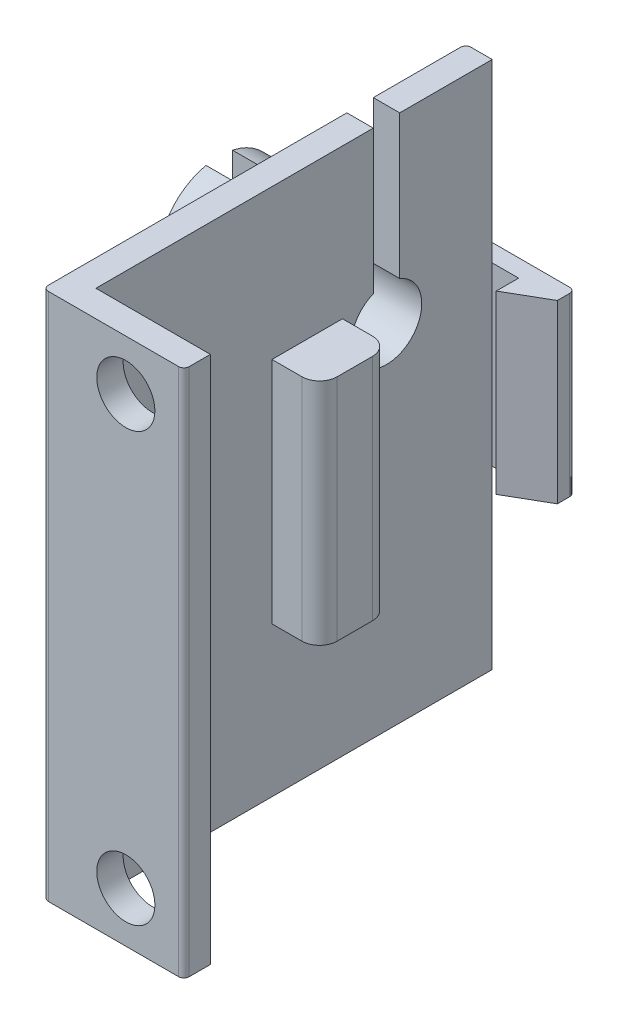
SolidWorks part; units mm, degrees
ref_plane "Front Plane" through (0, 0, 0) normal (0, 0, 1) x (1, 0, 0)
ref_plane "Top Plane" through (0, 0, 0) normal (0, 1, 0) x (1, 0, 0)
ref_plane "Right Plane" through (0, 0, 0) normal (1, 0, 0) x (0, 0, -1)
sketch "Sketch1" plane through (0, 0, 0) normal (0, 1, 0) x (1, 0, 0)
  line L0 (0, 0) -> (-2.2, 0)
  line L5 (-2.2, 0) -> (-2.2, -1.2702)
  line L6 (-2.2, -1.2702) -> (0, 0)
  dimension "D1" = 60
  dimension "D2" = 2.2
extrude "Boss-Extrude1" add sketch "Sketch1" along normal blind 5 and the other way blind 5
sketch "Sketch2" plane through (0, 0, 0) normal (0, 0, -1) x (-1, 0, 0)
  line L0 (0, 5) -> (2.2, 5) construction
  line L1 (0, -5) -> (3.7, -5)
  line L2 (0, -5) -> (0, 5)
  line L3 (0, 5) -> (3.7, 5)
  line L4 (3.7, -5) -> (3.7, 5)
  line L5 (0, -5) -> (3.7, 5) construction
  line L6 (0, 5) -> (3.7, -5) construction
  line L7 (2.2, -5) -> (2.2, 5) construction
  point P4 (1.85, 0)
  dimension "D1" = 1.5
extrude "Boss-Extrude2" add sketch "Sketch2" along normal blind 1
sketch "Sketch3" plane through (-3.7, 0, 0) normal (-1, 0, 0) x (0, 0, 1)
  line L0 (0, 0) -> (12.5427, 0) construction
  line L1 (0, -15) -> (22.5, -15)
  line L2 (0, -15) -> (0, 15)
  line L3 (0, 15) -> (22.5, 15)
  line L4 (22.5, -15) -> (22.5, 15)
  line L5 (0, -15) -> (22.5, 15) construction
  line L6 (0, 15) -> (22.5, -15) construction
  line L7 (0, -5) -> (0, 5) construction
  line L9 (0, 5) -> (-1, 5)
  line L10 (0, 5) -> (0, -5)
  line L11 (0, -5) -> (-1, -5)
  line L12 (-1, 5) -> (-1, -5)
  line L13 (0, 5) -> (-1, -5) construction
  line L14 (0, -5) -> (-1, 5) construction
  point P4 (11.25, 0)
  point P16 (-0.5, 0)
  line M6 (0, -5) -> (0, 5)
  line M7 (0, 5) -> (-1, 5)
  line M8 (-1, 5) -> (-1, -5)
  line M9 (-1, -5) -> (0, -5)
  dimension "D1" = 22.5
  dimension "D2" = 30
extrude "Boss-Extrude3" add sketch "Sketch3" along normal blind 1.5 contours L1 L4 L3 L2 M6 | M9 M6 M7 M8 region at (-3.7, 0, 11.25) region at (-3.7, 0, -0.5)
sketch "Sketch4" plane through (0, 0, 22.5) normal (0, 0, 1) x (1, 0, 0)
  line L0 (-4.45, 0) -> (3.106, 0) construction
  line L1 (-5.2, -15) -> (-3.7, -15)
  line L2 (-5.2, -15) -> (-5.2, 15)
  line L3 (-5.2, 15) -> (-3.7, 15)
  line L4 (-3.7, -15) -> (-3.7, 15)
  line L5 (-5.2, -15) -> (-3.7, 15) construction
  line L6 (-5.2, 15) -> (-3.7, -15) construction
  line L7 (-3.7, -15) -> (2.8, -15)
  line L8 (-3.7, -15) -> (-3.7, 15)
  line L9 (-3.7, 15) -> (2.8, 15)
  line L10 (2.8, -15) -> (2.8, 15)
  line L11 (-3.7, -15) -> (2.8, 15) construction
  line L12 (-3.7, 15) -> (2.8, -15) construction
  circle A0 centre (-0.5, 12.15) radius 1.65
  circle A1 centre (-0.5, -12.15) radius 1.65
  point P4 (-4.45, 0)
  point P11 (-0.45, 0)
  line M5 (-3.7, -15) -> (-3.7, 15)
  line M6 (-3.7, 15) -> (-5.2, 15)
  line M7 (-5.2, 15) -> (-5.2, -15)
  line M8 (-5.2, -15) -> (-3.7, -15)
  dimension "D4" = 3.3
  dimension "D1" = 30
  dimension "D2" = 6.5
  dimension "D3" = 3.3
  dimension "D5" = 2.85
extrude "Boss-Extrude4" add sketch "Sketch4" along normal blind 1.5 contours L7 L10 L9 M5 | M8 M5 M6 M7 region at (-4.45, 0, 22.5) region at (-0.4452, 0, 22.5)
ref_plane "Plane1" through (0, 0, 0) normal (0, 1, 0) x (1, 0, 0)
fillet "Fillet1" radius 0.3 6 edges at (-5.2, 0, -1) (-5.2, 0, 24) (-5.2, -10, 0) (-5.2, 10, 0) (2.8, 0, 24) (0, 0, -1)
sketch "Sketch5" plane through (-3.7, 0, 0) normal (1, 0, 0) x (0, 0, -1)
  line L5 (-10.5, -15) -> (-10.5, 15) construction
  line L7 (-12.5, 6.5) -> (-8.5, 6.5)
  line L8 (-12.5, 6.5) -> (-12.5, -6.5)
  line L9 (-12.5, -6.5) -> (-8.5, -6.5)
  line L10 (-8.5, 6.5) -> (-8.5, -6.5)
  line L11 (-12.5, 6.5) -> (-8.5, -6.5) construction
  line L12 (-12.5, -6.5) -> (-8.5, 6.5) construction
  line L14 (0, 15) -> (-22.5, 15) construction
  line L15 (0, 5) -> (0, 15) construction
  line L17 (0, -15) -> (-22.5, -15) construction
  point P6 (-10.5, 0)
  point P7 (-10.5, 0)
  point P12 (-10.5, 0)
  dimension "D1" = 13
  dimension "D2" = 4
  dimension "D3" = 10.5
extrude "Boss-Extrude5" add sketch "Sketch5" along normal blind 2.7 contours L8 L7 L10 L9
sketch "Sketch7" plane through (-3.7, 0, 0) normal (1, 0, 0) x (0, 0, -1)
  line L0 (0, 5) -> (0, 15) construction
  line L1 (0, 15) -> (-22.5, 15) construction
  line L2 (-6, 5) -> (-6, 15) construction
  line L3 (-6.75, 15) -> (-6.75, 6.854)
  line L4 (-5.25, 15) -> (-5.25, 6.854)
  line L5 (-6.75, 15) -> (-5.25, 15)
  circle A0 centre (-6, 5) radius 2
  circle A1 centre (-6, 5) radius 3.5
  line M6 (0, 15) -> (-22.5, 15)
  line M11 (-12.5, 6.5) -> (-8.5, 6.5)
  line M12 (-8.5, 6.5) -> (-8.5, -6.5)
  dimension "D1" = 4
  dimension "D6" = 1.5
  dimension "D2" = 6
  dimension "D3" = 10
  dimension "D4" = 0.75
  dimension "D5" = 1.5
extrude "Cut-Extrude1" cut sketch "Sketch7" against normal through all contours A0 | A1 L2 L5 L3 | L2 A1 L4 M6 | L2 A0 L4 A1 | A0 L2 A1 L3 region at (-3.7, 7.7121, 6.3776) region at (-3.7, 7.7121, 5.6224) region at (-3.7, 6.9076, 5.6288) region at (-3.7, 11.7365, 6.3758) region at (-3.7, 11.7365, 5.6242)
extrude "Boss-Extrude6" add sketch "Sketch7<3>" against normal blind 8 from surface contours L3 A1 L4 A0 | A1 M11 M12 region at (-3.7, 7.6364, 6.846) region at (-3.7, 4.7864, 8.9253) starting at face at (-5.2, 3.3212, 5.9333)
sketch "Sketch7<3>" plane through (-3.7, 0, 0) normal (1, 0, 0) x (0, 0, -1) same geometry as "Sketch7"
ref_plane "Plane2" through (0, 1.5, 0) normal (0, -1, 0) x (-1, 0, 0)
sketch "Sketch8" plane through (0, 1.5, 0) normal (0, -1, 0) x (-1, 0, 0)
  line L0 (13.2, -2.5) -> (5.2, -2.5) construction
  line L1 (13.2, -2.5) -> (8.4, -2.5)
  line L2 (13.2, -2.5) -> (13.2, -9.5)
  line L3 (13.2, -9.5) -> (8.4, -9.5)
  line L4 (8.4, -2.5) -> (8.4, -9.5)
  line L5 (13.2, -2.5) -> (8.4, -9.5) construction
  line L6 (13.2, -9.5) -> (8.4, -2.5) construction
  line L7 (13.2, -9.5) -> (13.2, -2.5) construction
  point P4 (10.8, -6)
  point P9 (0, 0)
  point P10 (0, 0)
  point P11 (0, 0)
  point P12 (7.5299, -7.7563)
  point P13 (7.4307, -2.5)
  point P14 (7.1111, -2.5)
  point P15 (0, 0)
  point P16 (0, 0)
  point P18 (7.1864, -9.5)
  dimension "D1" = 4.8
ref_axis "Axis1" through (-13.2, 5, 6) along (1, 0, 0)
ref_plane "Plane3" through (0, 5, 0) normal (0, 1, 0) x (1, 0, 0)
extrude "Cut-Extrude2" cut sketch "Sketch8" against normal up to surface (3.5 mm away) up to plane "Plane3"
fillet "Fillet4" radius 1 2 edges at (-1, 0, 12.5) (-1, 0, 8.5)
chamfer "Chamfer1" distance 2 angle 45 2 edges at (-8.4, 5, 8.75) (-8.4, 5, 3.25)
chamfer "Chamfer3" distance 1 angle 45 1 edges at (-5.2, 1.5, 6)
equation "\"WallThick\"= 1.2'thickness of wall for printer"
equation "\"dHole\"= 3.3'diameter of screw hole"
equation "\"dCable\"= 1.5"
equation "\"FillHole\"= 8'Height of fill hole to seal with hot glue"
equation "\"D1@Sketch8\"=0.6*\"FillHole\""
equation "\"D1@Boss-Extrude6\"=\"FillHole\""
